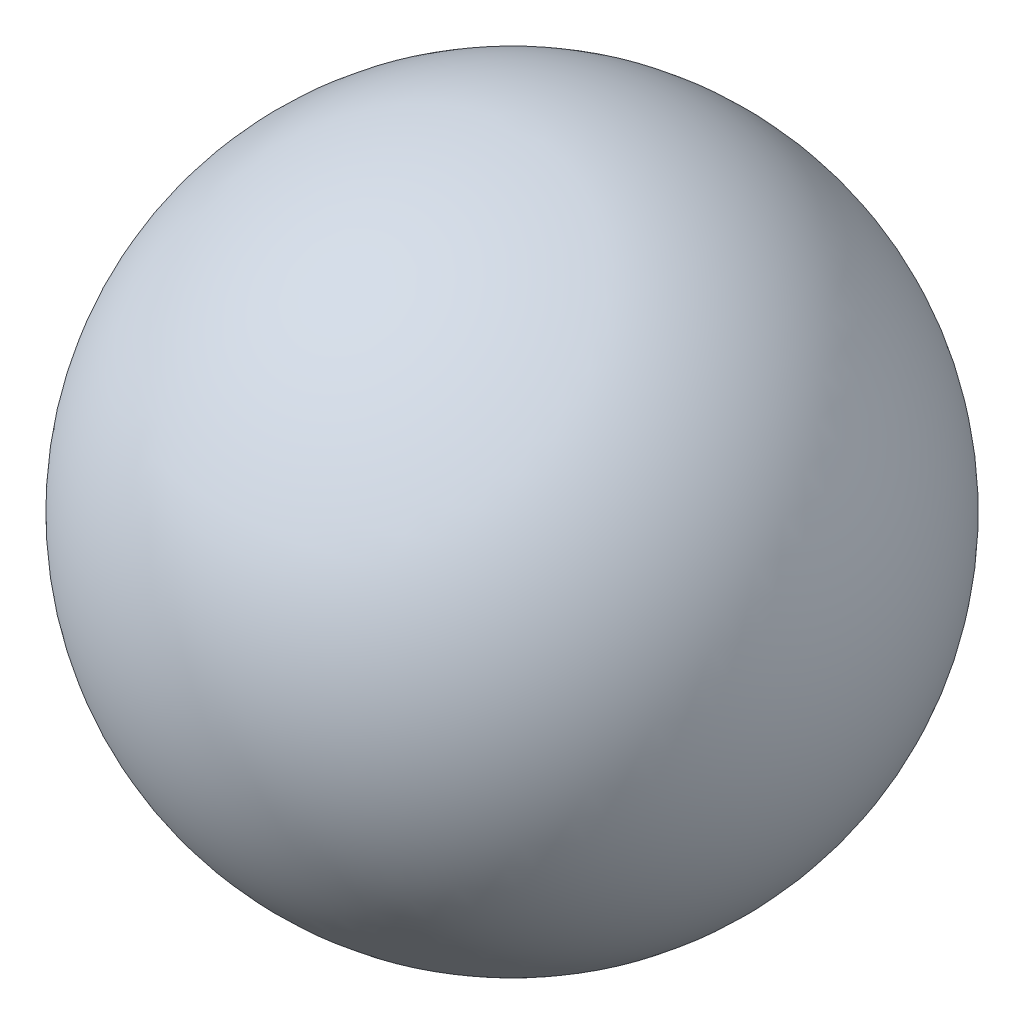
SolidWorks part; units mm, degrees
ref_plane "前视基准面" through (0, 0, 0) normal (0, 0, 1) x (1, 0, 0)
ref_plane "上视基准面" through (0, 0, 0) normal (0, 1, 0) x (1, 0, 0)
ref_plane "右视基准面" through (0, 0, 0) normal (1, 0, 0) x (0, 0, -1)
sketch "草图1" plane through (0, 0, 0) normal (0, 0, 1) x (1, 0, 0)
  line L0 (0, 124.4874) -> (0, -127.4975) construction
  line L1 (0, 108) -> (0, -108)
  arc A0 (0, -108) -> (0, 108) centre (0, 0) ccw
  dimension "D1" = 216
revolve "旋转1" add sketch "草图1" angle 360 about L0
ref_plane "基准面1" through (0, 0, 34) normal (0, 0, 1) x (1, 0, 0)
ref_axis "基准轴1" through (0, -118.8, 0) along (0, 1, 0)
ref_point "点1"
